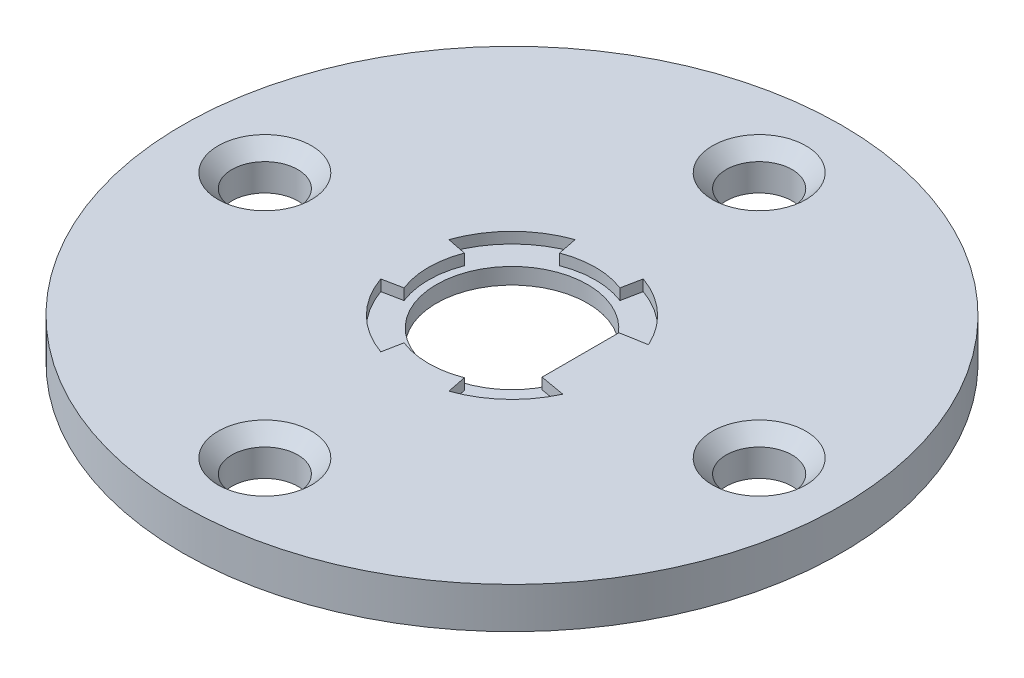
SolidWorks part; units mm, degrees
ref_plane "Front Plane" through (0, 0, 0) normal (0, 0, 1) x (1, 0, 0)
ref_plane "Top Plane" through (0, 0, 0) normal (0, 1, 0) x (1, 0, 0)
ref_plane "Right Plane" through (0, 0, 0) normal (1, 0, 0) x (0, 0, -1)
sketch "Sketch1" plane through (0, 0, 0) normal (0, 1, 0) x (1, 0, 0)
  circle A0 centre (0, 0) radius 24
  circle A1 centre (-18, 0) radius 2 construction
  circle A2 centre (0, -18) radius 2 construction
  circle A3 centre (18, 0) radius 2 construction
  circle A4 centre (0, 18) radius 2 construction
  circle A5 centre (-18, 0) radius 2 construction
  circle A6 centre (0, -18) radius 2 construction
  circle A7 centre (18, 0) radius 2 construction
  circle A8 centre (0, 18) radius 2 construction
  circle A9 centre (0, 18) radius 2.4
  circle A10 centre (-18, 0) radius 2.4
  circle A11 centre (0, -18) radius 2.4
  circle A12 centre (18, 0) radius 2.4
  dimension "D1" = 48
  dimension "D2" = 0.4
extrude "Boss-Extrude1" add sketch "Sketch1" along normal up to surface (2.98 mm away)
ref_axis "center" through (0, 1.05, 0) along (0, -1, 0)
sketch "Sketch2" plane through (0, 2.98, 0) normal (0, 1, 0) x (1, 0, 0)
  line L0 (4.99, 2.7984) -> (4.99, -2.7984)
  line L1 (4.915, 3.441) -> (4.915, -3.441) construction
  line L2 (0, 0) -> (2.9294, 0) construction
  line L3 (0, 0) -> (0, -2.8793) construction
  line L4 (0, 0) -> (-9.3067, 9.3067) construction
  line L5 (-2.1984, 5.6633) -> (-5.6633, 2.1984) construction
  line L6 (-2.1984, 5.6633) -> (-2.4791, 7.0784)
  line L7 (-2.1984, 5.6633) -> (0, 0) construction
  line L8 (-5.6633, 2.1984) -> (-7.0784, 2.4791)
  line L9 (-5.6633, 2.1984) -> (0, 0) construction
  line L10 (-5.6633, -2.1984) -> (-7.0784, -2.4791)
  line L11 (-2.1984, -5.6633) -> (-2.4791, -7.0784)
  line L12 (2.1984, 5.6633) -> (2.4791, 7.0784)
  line L13 (2.1984, 5.6633) -> (4.99, 2.7984) construction
  line L14 (4.99, 2.7984) -> (6.8197, 3.1211)
  line L15 (4.99, -2.7984) -> (6.8197, -3.1211)
  line L16 (2.1984, -5.6633) -> (2.4791, -7.0784)
  circle A0 centre (0, 0) radius 6.075 construction
  circle A6 centre (0, 0) radius 7.5 construction
  arc A7 (-5.6633, 2.1984) -> (-5.6633, -2.1984) centre (0, 0) ccw
  arc A8 (-2.1984, 5.6633) -> (2.1984, 5.6633) centre (0, 0) cw
  arc A9 (-2.1984, -5.6633) -> (2.1984, -5.6633) centre (0, 0) ccw
  arc A10 (-2.4791, 7.0784) -> (-7.0784, 2.4791) centre (0, 0) ccw
  arc A11 (-2.4791, -7.0784) -> (-7.0784, -2.4791) centre (0, 0) cw
  arc A12 (2.4791, 7.0784) -> (6.8197, 3.1211) centre (0, 0) cw
  arc A13 (2.4791, -7.0784) -> (6.8197, -3.1211) centre (0, 0) ccw
  dimension "D1" = 12.15
  dimension "D3" = 15
  dimension "D4" = 45
  dimension "D2" = 0.075
  dimension "D5" = 4.9
  dimension "D6" = 170
  dimension "D7" = 4
  dimension "D8" = 100
extrude "Cut-Extrude1" cut sketch "Sketch2" against normal blind 0.8
sketch "Sketch3" plane through (0, 2.18, 0) normal (0, 1, 0) x (1, 0, 0)
  circle A2 centre (0, 0) radius 5.5
  dimension "D1" = 11
extrude "Cut-Extrude2" cut sketch "Sketch3" against normal through all
chamfer "Chamfer1" distance 1 angle 45 4 edges at (0, 2.98, 20.4) (18, 2.98, 2.4) (0, 2.98, -15.6) (-18, 2.98, 2.4)
sketch "Sketch4" plane through (0, 0, 0) normal (0, -1, 0) x (1, 0, 0)
  circle A0 centre (0, 0) radius 12
  dimension "D1" = 24
extrude "Cut-Extrude3" cut sketch "Sketch4" against normal blind 1
